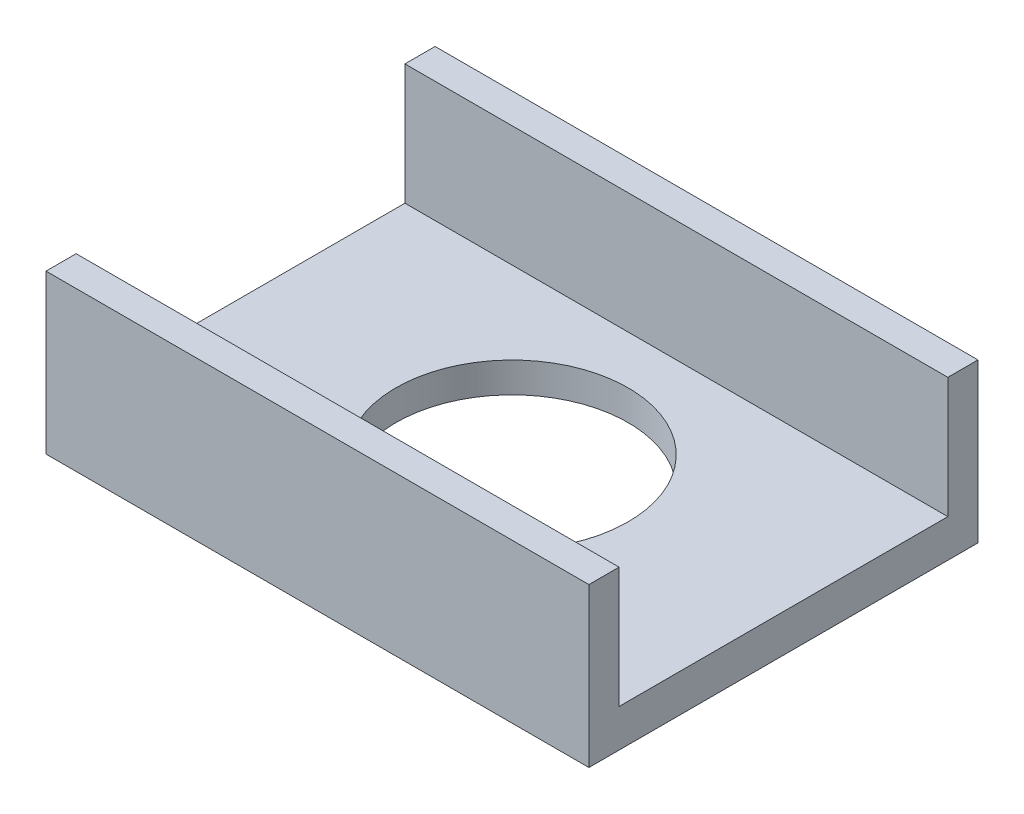
SolidWorks part; units mm, degrees
note: The reader was unsure of these and kept them because the rebuilt part matched: shared geometry of "Sketch1<5>".
ref_plane "Front Plane" through (0, 0, 0) normal (0, 0, 1) x (1, 0, 0)
ref_plane "Top Plane" through (0, 0, 0) normal (0, 1, 0) x (1, 0, 0)
ref_plane "Right Plane" through (0, 0, 0) normal (1, 0, 0) x (0, 0, -1)
sketch "Sketch1" plane through (0, 0, 0) normal (0, 1, 0) x (1, 0, 0)
  line L1 (-40, 27.25) -> (40, 27.25)
  line L2 (-40, 27.25) -> (-40, -27.25)
  line L3 (-40, -27.25) -> (40, -27.25)
  line L4 (40, 27.25) -> (40, -27.25)
  line L5 (-40, 27.25) -> (40, -27.25) construction
  line L6 (-40, -27.25) -> (40, 27.25) construction
  circle A0 centre (0, 0) radius 19.25
  point P0 (0, 0)
  dimension "D3" = 38.5
  dimension "D1" = 80
  dimension "D2" = 54.5
extrude "Boss-Extrude1" add sketch "Sketch1" against normal blind 1.27 contours L4 L1 L2 L3 A0 | A0
shell "Shell4" thickness 5 removed face at (0, -1.27, 0) outward yes
sketch "Sketch7" plane through (0, 5, 0) normal (0, 1, 0) x (1, 0, 0)
  line L0 (-40, 27.25) -> (-40, -27.25)
  line L1 (-40, -27.25) -> (40, -27.25)
  line L2 (40, -27.25) -> (40, 27.25)
  line L3 (40, 27.25) -> (-40, 27.25)
  line L4 (45, -32.25) -> (45, 32.25)
  line L5 (45, 32.25) -> (-45, 32.25)
  line L6 (-45, 32.25) -> (-45, -32.25)
  line L7 (-45, -32.25) -> (45, -32.25)
  line L8 (45, -32.25) -> (45, 32.25)
  line L9 (45, 32.25) -> (-45, 32.25)
  line L10 (-45, 32.25) -> (-45, -32.25)
  line L11 (-45, -32.25) -> (45, -32.25)
  line L12 (-40, -27.25) -> (-40, 27.25)
  line L13 (-40, -27.25) -> (-45.036, -27.25)
  line L14 (-40, 27.25) -> (-45.036, 27.25)
  line L15 (-45.036, -27.25) -> (-45.036, 27.25)
  line L16 (0, -55) -> (0, 55) construction
  line L17 (40, 27.25) -> (45.036, 27.25)
  line L18 (45.036, -27.25) -> (45.036, 27.25)
  line L19 (40, -27.25) -> (45.036, -27.25)
  line L20 (40, -27.25) -> (40, 27.25)
  line M9 (45, -32.25) -> (45, 32.25)
  line M10 (45, 32.25) -> (-45, 32.25)
  line M11 (-45, 32.25) -> (-45, -32.25)
  line M12 (-45, -32.25) -> (45, -32.25)
  dimension "D1" = 0
  dimension "D2" = 5
extrude "Boss-Extrude4" add sketch "Sketch7" along normal blind 20 contours L14 L3 L2 L1 L13 L10 M12 M9 M10 M11 | L19 L1 L13 L10 M12 M9
extrude "Cut-Extrude3" cut sketch "Sketch1<5>" against normal through all both and the other way through all contours A0
sketch "Sketch1<5>" plane through (0, 0, 0) normal (0, 1, 0) x (1, 0, 0) same geometry as "Sketch1"
hole_wizard "Ø4.0mm Dowel Hole1" positions "Sketch8" profile "Sketch9" hole size "Ø4.0" standard "ANSI Metric"
sketch "Sketch8" plane through (0, 0, -27.25) normal (0, 0, 1) x (1, 0, 0)
  line L0 (-40, -20) -> (40, -20) construction
  line L1 (0, -20) -> (0, 0) construction
  line L2 (-40, 0) -> (40, 0) construction
  point P0 (-20, -10)
  point P13 (20, -10)
  dimension "D1" = 20
  dimension "D2" = 10
sketch "Sketch9" plane through (-20, -10, -27.25) normal (1, 0, 0) x (0, -1, 0)
  line L0 (0, 0) -> (0, 5)
  line L1 (0, 5) -> (2, 5)
  line L2 (2, 5) -> (2, 0)
  line L5 (2, 0) -> (0, 0)
  line L11 (0, -6.35) -> (0, 107.95) construction
  dimension "Thru Hole Dia." = 4
  dimension "Thru Hole Depth" = 5
mirror "Mirror1" about plane through (0, 0, 0) normal (0, 0, 1)
